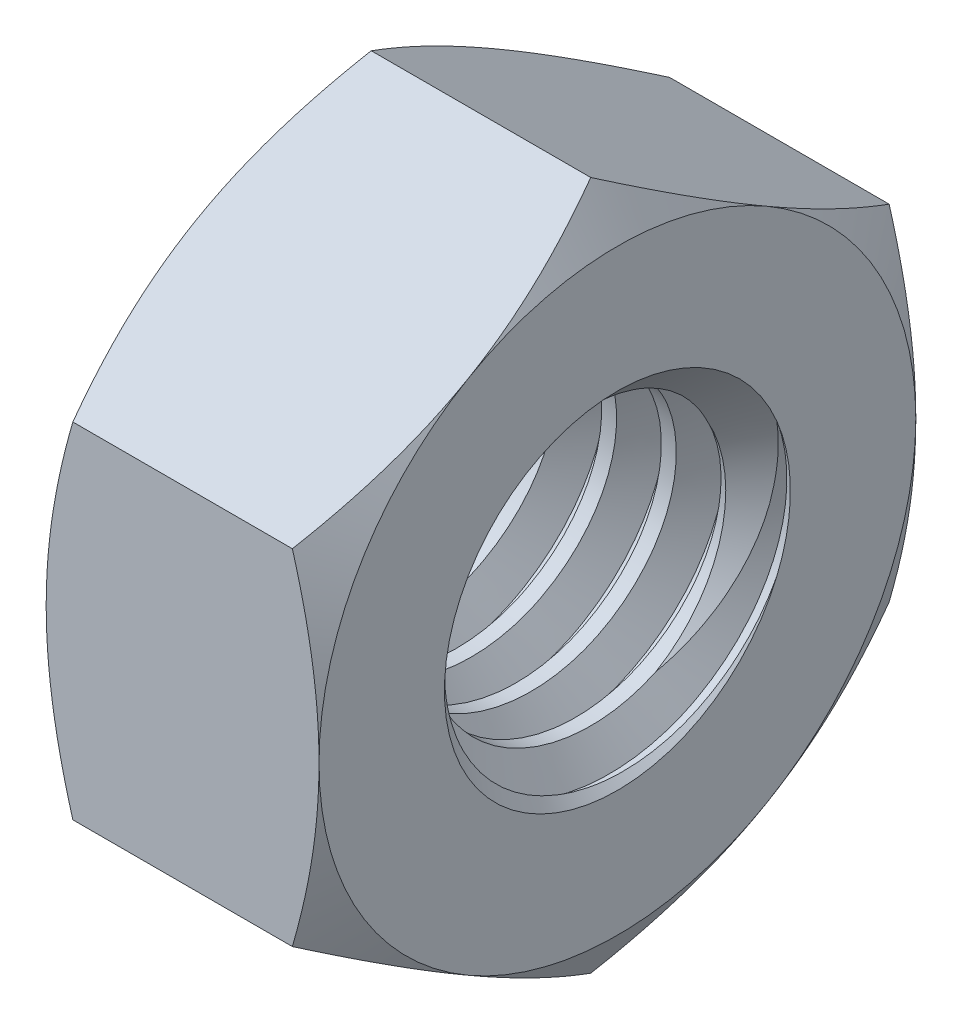
SolidWorks part; units mm, degrees
material "Plain Carbon Steel"
ref_plane "Front Plane" through (0, 0, 0) normal (0, 0, 1) x (1, 0, 0)
ref_plane "Top Plane" through (0, 0, 0) normal (0, 1, 0) x (1, 0, 0)
ref_plane "Right Plane" through (0, 0, 0) normal (1, 0, 0) x (0, 0, -1)
sketch "Sketch1" plane through (0, 0, 0) normal (1, 0, 0) x (0, 0, -1)
  line L0 (3.5, 2.0207) -> (3.5, -2.0207)
  line L1 (-3.5, 2.0207) -> (-3.5, -2.0207)
  line L2 (3.5, 2.0207) -> (0, 4.0415)
  line L3 (0, 4.0415) -> (-3.5, 2.0207)
  line L4 (-3.5, -2.0207) -> (0, -4.0415)
  line L5 (0, -4.0415) -> (3.5, -2.0207)
  circle A0 centre (0, 0) radius 1.65
  dimension "D3" = 3.3
  dimension "D1" = 7
  dimension "D2" = 120
  dimension "D4" = 3.5
extrude "Boss-Extrude1" add sketch "Sketch1" along normal mid plane 3.2
sketch "Sketch2" plane through (-1.6, 0, 0) normal (-1, 0, 0) x (0, 0, 1)
  line L0 (-3.5, -2.0207) -> (-3.5, 2.0207) construction
  line L1 (-3.5, 2.0207) -> (0, 4.0415) construction
  line L2 (0, 4.0415) -> (3.5, 2.0207) construction
  line L3 (3.5, 2.0207) -> (3.5, -2.0207) construction
  line L4 (3.5, -2.0207) -> (0, -4.0415) construction
  line L5 (0, -4.0415) -> (-3.5, -2.0207) construction
  line L6 (-3.5, -2.0207) -> (-3.5, 2.0207) construction
  line L7 (-3.5, 2.0207) -> (0, 4.0415) construction
  line L8 (0, 4.0415) -> (3.5, 2.0207) construction
  line L9 (3.5, 2.0207) -> (3.5, -2.0207) construction
  line L10 (3.5, -2.0207) -> (0, -4.0415) construction
  line L11 (0, -4.0415) -> (-3.5, -2.0207) construction
  circle A0 centre (0, 0) radius 3.5 construction
sketch "Sketch4" plane through (0, 0, 0) normal (0, 0, 1) x (1, 0, 0)
  line L0 (-1.6, 3.5) -> (-1.6, -3.5) construction
  line L1 (-1.6, 3.5) -> (-1.6, -3.5) construction
  line L2 (-1.6, 3.5) -> (-1.6, 5.2275)
  line L3 (-1.6, 5.2275) -> (-0.6026, 5.2275)
  line L4 (-0.6026, 5.2275) -> (-1.6, 3.5)
  line L5 (-2.7191, 0) -> (4.5055, 0) construction
  dimension "D1" = 30
revolve "Cut-Revolve1" cut sketch "Sketch4" angle 360 about L5
mirror "Mirror1" about plane through (0, 0, 0) normal (1, 0, 0) of "Cut-Revolve1"
ref_plane "Plane1" through (2.3, 0, 0) normal (1, 0, 0) x (0, 0, -1)
chamfer "Chamfer1" distance 0.379 angle 45 2 edges at (-1.6, 0, -1.65) (1.6, 0, -1.65)
sketch "Sketch5" plane through (2.3, 0, 0) normal (1, 0, 0) x (0, 0, -1)
  circle A0 centre (0, 0) radius 1.65 construction
  circle A1 centre (0, 0) radius 1.65
curve "Helix/Spiral1" pitch 0.7 height 5 radius 1.65 centre (2.3, 0, 0) axis (-1, 0, 0) start towards (0, 0, -1)
sketch "Sketch7" plane through (0, 0, 0) normal (0, 1, 0) x (1, 0, 0)
  line L0 (2.3, -1.65) -> (2.3, 1.65) construction
  line L2 (2.3, -1.65) -> (2.3, 1.65) construction
  line L3 (-3.8262, 1.65) -> (4.8666, 1.65) construction
  line L4 (1.6335, 0.9504) -> (2.9665, 0.9504)
  line L5 (2.9665, 0.9504) -> (2.3437, 2.029)
  line L6 (1.6335, 0.9504) -> (2.2562, 2.029)
  line L7 (2.3437, 2.029) -> (2.2562, 2.029)
  point P9 (2.3, 0.9504)
  point P11 (2.3, 2.029)
  dimension "D1" = 0.0875
  dimension "D2" = 60
  dimension "D3" = 0.379
sweep "Cut-Sweep1" cut profiles "Sketch7" path "Helix/Spiral1" align with end faces yes
